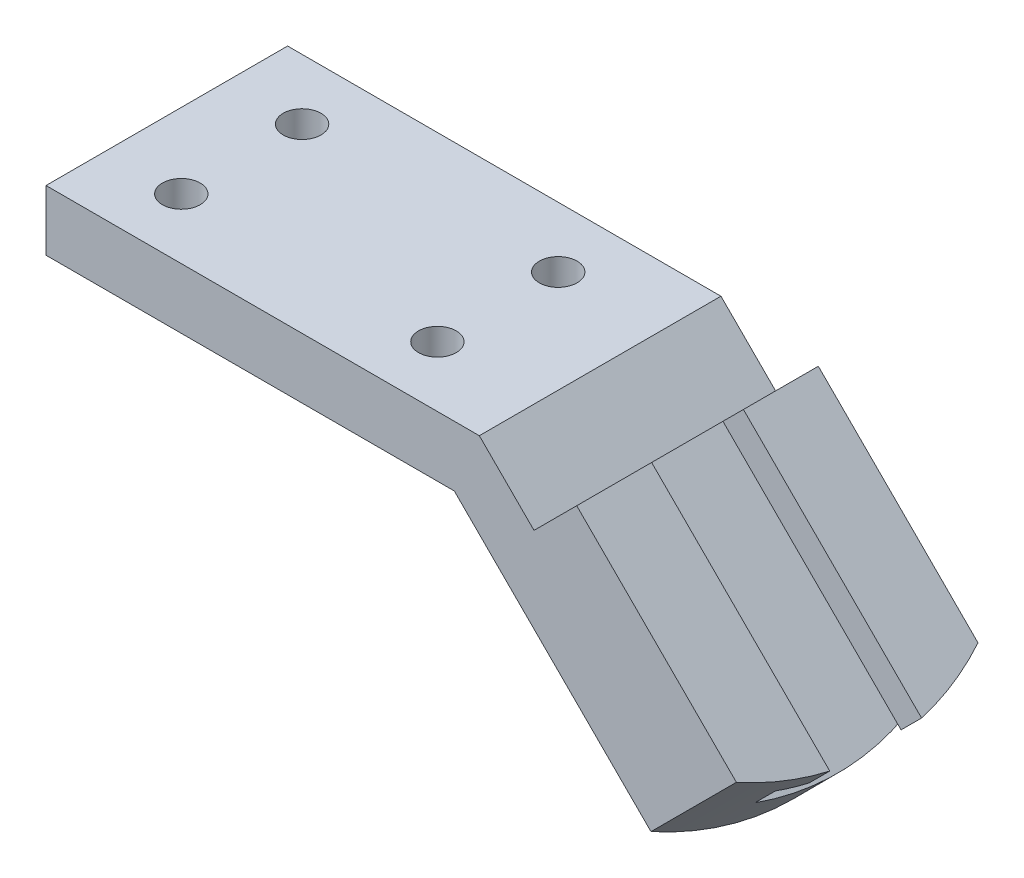
SolidWorks part; units mm, degrees
ref_plane "Front Plane" through (0, 0, 0) normal (0, 0, 1) x (1, 0, 0)
ref_plane "Top Plane" through (0, 0, 0) normal (0, 1, 0) x (1, 0, 0)
ref_plane "Right Plane" through (0, 0, 0) normal (1, 0, 0) x (0, 0, -1)
sketch "Sketch1" plane through (0, 0, 0) normal (0, 0, 1) x (1, 0, 0)
  line L0 (0, 0) -> (85.852, 0)
  line L1 (85.852, 0) -> (131.7033, -45.8513)
  line L2 (131.7033, -45.8513) -> (149.6638, -27.8908)
  line L3 (149.6638, -27.8908) -> (111.5875, 10.1855)
  line L4 (111.5875, 10.1855) -> (102.6072, 1.2053)
  line L5 (102.6072, 1.2053) -> (91.1125, 12.7)
  line L6 (91.1125, 12.7) -> (0, 12.7)
  line L7 (0, 12.7) -> (0, 0)
  dimension "D1" = 12.7
  dimension "D2" = 85.852
  dimension "D3" = 25.4
  dimension "D4" = 12.7
  dimension "D5" = 70.104
  dimension "D6" = 45
  dimension "D7" = 53.848
extrude "Boss-Extrude1" add sketch "Sketch1" along normal mid plane 50.8
sketch "Sketch2" plane through (60.8865, 60.8865, 0) normal (0.7071, 0.7071, 0) x (0, 0, -1)
  line L0 (-25.4, -71.702) -> (25.4, -71.702) construction
  line L1 (-25.4, -125.55) -> (-25.4, -119.183)
  line L2 (-25.4, -125.55) -> (-25.4, -71.702) construction
  line L3 (-25.4, -125.55) -> (0, -125.55)
  line L4 (25.4, -125.55) -> (25.4, -119.183)
  line L5 (25.4, -125.55) -> (25.4, -71.702) construction
  line L6 (0, -125.55) -> (25.4, -125.55)
  line L7 (9.652, -71.702) -> (-9.652, -71.702)
  line L8 (9.652, -71.702) -> (9.652, -124.6779)
  line L9 (-9.652, -124.6779) -> (-9.652, -125.55)
  line L10 (-9.652, -71.702) -> (-9.652, -124.6779)
  line L11 (9.652, -124.6779) -> (9.652, -125.55)
  arc A0 (-25.4, -119.183) -> (-9.652, -124.6779) centre (0, -71.702) ccw
  arc A1 (9.652, -124.6779) -> (25.4, -119.183) centre (0, -71.702) ccw
  arc A2 (9.652, -124.6779) -> (-9.652, -124.6779) centre (0, -71.702) cw
  point P17 (0, -71.702)
  line M1 (25.4, -125.55) -> (25.4, -71.702)
  line M2 (25.4, -71.702) -> (-25.4, -71.702)
  line M3 (-25.4, -71.702) -> (-25.4, -125.55)
  line M4 (-25.4, -125.55) -> (25.4, -125.55)
  dimension "D1" = 53.848
  dimension "D2" = 19.304
extrude "Cut-Extrude2" cut sketch "Sketch2" against normal blind 12.192 contours A0 L9 M3 M4 | L11 L8 L10 L9 L3 M2 M4 | A1 L11 L6 M1 | L3 A2 L9 | L11 A2 M4 region at (148.2633, -26.4903, 19.7954) region at (149.479, -27.706, 7.2429) region at (130.5236, -8.7506, 0) region at (149.479, -27.706, -7.2429) region at (148.2633, -26.4903, -19.7954)
extrude "Cut-Extrude3" cut sketch "Sketch2<5>" against normal through all contours L3 A2 L9 | A0 L9 M3 M4 | A1 L11 L6 M1 | L11 A2 M4 region at (148.2633, -26.4903, 19.7954) region at (149.479, -27.706, 7.2429) region at (149.479, -27.706, -7.2429) region at (148.2633, -26.4903, -19.7954)
sketch "Sketch2<5>" plane through (60.8865, 60.8865, 0) normal (0.7071, 0.7071, 0) x (0, 0, -1) same geometry as "Sketch2"
sketch "Sketch3" plane through (50.701, -50.701, 0) normal (-0.7071, 0.7071, 0) x (0, 0, 1)
  line L0 (-9.652, 73.9145) -> (9.652, 73.9145) construction
  line L1 (-15.748, 73.9145) -> (15.748, 73.9145)
  line L2 (-15.748, 73.9145) -> (-15.748, 80.0105)
  line L3 (-15.748, 80.0105) -> (15.748, 80.0105)
  line L4 (15.748, 73.9145) -> (15.748, 80.0105)
  point P4 (0, 80.0105)
  dimension "D1" = 6.096
  dimension "D2" = 31.496
extrude "Cut-Extrude4" cut sketch "Sketch3" against normal through all
sketch "Sketch4" plane through (0, 12.7, 0) normal (0, 1, 0) x (1, 0, 0)
  line L0 (15.748, 12.7) -> (15.748, -12.7) construction
  line L1 (15.748, -12.7) -> (69.596, -12.7) construction
  line L2 (69.596, -12.7) -> (69.596, 12.7) construction
  line L3 (69.596, 12.7) -> (15.748, 12.7) construction
  line L4 (91.1125, -25.4) -> (0, -25.4) construction
  line L5 (0, -25.4) -> (0, 25.4) construction
  circle A0 centre (15.748, 12.7) radius 3.9688
  circle A1 centre (69.596, 12.7) radius 3.9687
  circle A2 centre (15.748, -12.7) radius 3.9688
  circle A3 centre (69.596, -12.7) radius 3.9687
  dimension "D1" = 7.9375
  dimension "D2" = 53.848
  dimension "D3" = 25.4
  dimension "D4" = 12.7
  dimension "D5" = 15.748
extrude "Cut-Extrude5" cut sketch "Sketch4" against normal through all
